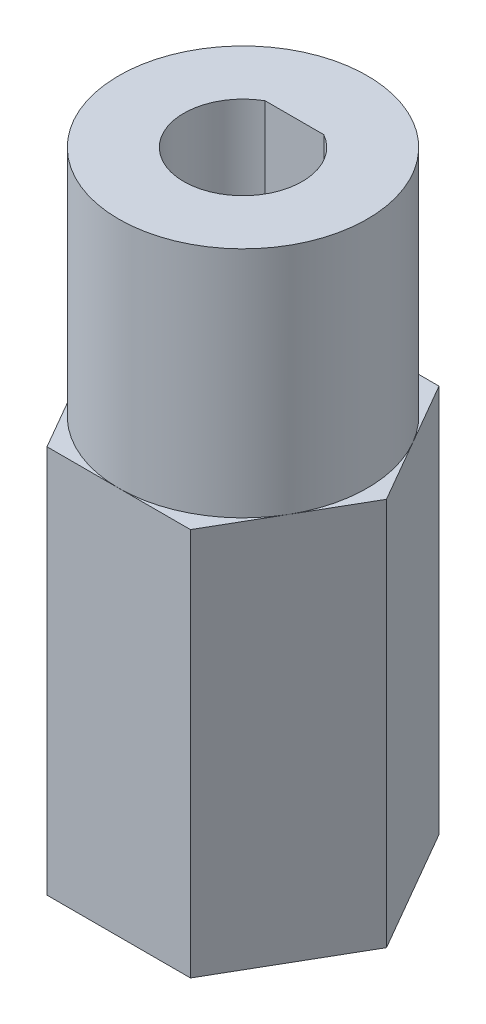
SolidWorks part; units mm, degrees
ref_plane "Front Plane" through (0, 0, 0) normal (0, 0, 1) x (1, 0, 0)
ref_plane "Top Plane" through (0, 0, 0) normal (0, 1, 0) x (1, 0, 0)
ref_plane "Right Plane" through (0, 0, 0) normal (1, 0, 0) x (0, 0, -1)
sketch "Sketch1" plane through (0, 0, 0) normal (0, 1, 0) x (1, 0, 0)
  line L1 (3.695, -6.4) -> (7.3901, 0)
  line L2 (7.3901, 0) -> (3.695, 6.4)
  line L3 (3.695, 6.4) -> (-3.695, 6.4)
  line L4 (-3.695, 6.4) -> (-7.3901, 0)
  line L5 (-7.3901, 0) -> (-3.695, -6.4)
  line L6 (-3.695, -6.4) -> (3.695, -6.4)
  circle A0 centre (0, 0) radius 6.4 construction
  circle A1 centre (0, 0) radius 1.35
  dimension "D2" = 2.7
  dimension "D1" = 12.8
extrude "Boss-Extrude1" add sketch "Sketch1" along normal blind 20
sketch "Sketch2" plane through (0, 20, 0) normal (0, 1, 0) x (1, 0, 0)
  circle A0 centre (0, 0) radius 3.05
  circle A1 centre (0, 0) radius 6.4
  dimension "D1" = 6.1
extrude "Boss-Extrude2" add sketch "Sketch2" along normal blind 12
sketch "Sketch3" plane through (0, 32, 0) normal (0, 1, 0) x (1, 0, 0)
  line L0 (-1.51, 2.65) -> (1.51, 2.65)
  circle A0 centre (0, 0) radius 3.05 construction
  circle A1 centre (0, 0) radius 3.05 construction
  arc A2 (1.51, 2.65) -> (-1.51, 2.65) centre (0, 0) ccw
  point P6 (0, 3.05)
  dimension "D1" = 0.4
extrude "Boss-Extrude3" add sketch "Sketch3" against normal up to next
sketch "Sketch5" plane through (0, 0, -2.65) normal (0, 0, 1) x (1, 0, 0)
  circle A0 centre (0, 27) radius 1.5
  point P2 (0, 0)
  point P3 (0, 0)
  dimension "D1" = 3
  dimension "D2" = 27
extrude "Cut-Extrude1" cut sketch "Sketch5" against normal blind 12
